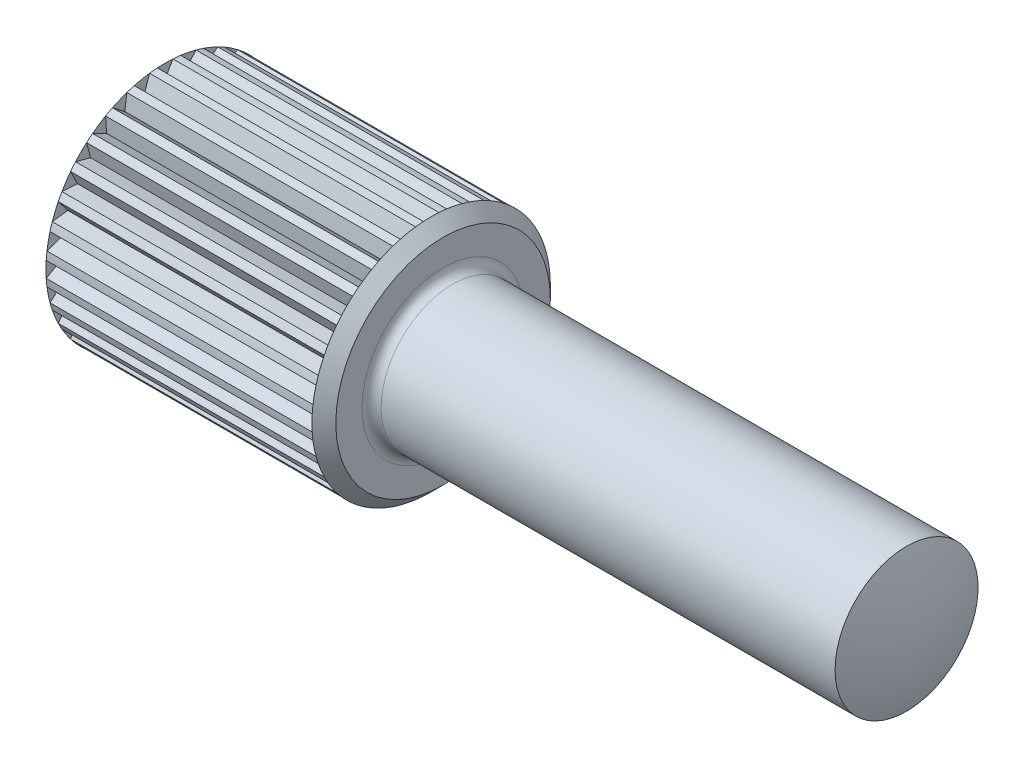
SolidWorks part; units mm, degrees
ref_plane "Front" through (0, 0, 0) normal (0, 0, 1) x (1, 0, 0)
ref_plane "Top" through (0, 0, 0) normal (0, 1, 0) x (1, 0, 0)
ref_plane "Right" through (0, 0, 0) normal (1, 0, 0) x (0, 0, -1)
sketch "Sketch1" plane through (0, 0, 0) normal (0, 0, 1) x (1, 0, 0)
  line L0 (0, 0) -> (33, 0)
  line L1 (1.3397, 5) -> (13, 5)
  line L2 (13, 5) -> (13, 3)
  line L7 (13, 3) -> (32.446, 3)
  line L9 (-48.2111, 0) -> (101.1311, 0) construction
  arc A0 (33, 0) -> (32.446, 3) centre (24.6, 0) ccw
  arc A1 (1.3397, 5) -> (0, 0) centre (10, 0) ccw
  dimension "l" = 20
  dimension "k" = 13
revolve "Base" add sketch "Sketch1" angle 360 about L9
cosmetic thread "ThreadCosmetic1" [suppressed] parameters "THD_MINOR"=4.5
chamfer "Chamfer1" distance 0.5 angle 45 1 edges at (13, 0, 5)
ref_plane "Plane1" through (1.3397, 0, 0) normal (1, 0, 0) x (0, 0, -1)
ref_plane "Plane2" through (12.5, 0, 0) normal (1, 0, 0) x (0, 0, -1)
sketch "Sketch2" plane through (1.3397, 0, 0) normal (1, 0, 0) x (0, 0, -1)
  line L1 (0, 4.4226) -> (0.5, 5.2887)
  line L2 (0.5, 5.2887) -> (-0.5, 5.2887)
  line L3 (-0.5, 5.2887) -> (0, 4.4226)
  circle A0 centre (0, 0) radius 5 construction
  circle A2 centre (0, 5) radius 0.2887 construction
  dimension "D1" = 1
extrude "Cut-Extrude1" cut sketch "Sketch2" along normal up to surface (11.1603 mm away) up to plane "Plane2"
pattern_circular "Circular-Pattern1" count 32 over 360 about axis through (-48.2111, 0, 0) along (1, 0, 0) of "Cut-Extrude1"
fillet "Fillet1" radius 0.4 1 edges at (13, 0, 3)
sketch "Sketch3" plane through (0, 0, 0) normal (0, 0, 1) x (1, 0, 0)
  line L0 (13.4, 3.75) -> (14.15, 3.75)
  line L1 (14.15, 3.75) -> (14.15, 3)
  line L2 (14.15, 3) -> (13.775, 2.3505)
  line L3 (13.775, 2.3505) -> (13.4, 3)
  line L4 (13.4, 3) -> (13.4, 3.75)
  line L5 (13.4, -3) -> (13.4, 3) construction
  line L6 (32.446, 3) -> (13.4, 3) construction
  dimension "D1" = 0.75
revolve "Cut-Revolve10" [suppressed] cut sketch "Sketch3" angle 360 about axis through (-48.2111, 0, 0) along (1, 0, 0)
pattern_linear "LPattern10" [suppressed] count 22 along (1, 0, 0) of bodies 104
equation "\"D1@Circular-Pattern1\" =int (  \"dk@Sketch1\" * PI+1 )"
equation "\"D1@Plane2\" = \"c@Chamfer1\""
equation "\"D1@Sketch3\" =  ( \"d@Sketch1\" - \"THD_MINOR@ThreadCosmetic1\" )  / 2"
equation "\"pitch@LPattern10\" = 1.2 * \"D1@Sketch3\""
equation "\"D1@LPattern10\" =  ( \"l@Sketch1\" - \"r@Fillet1\" )  / \"pitch@LPattern10\""
